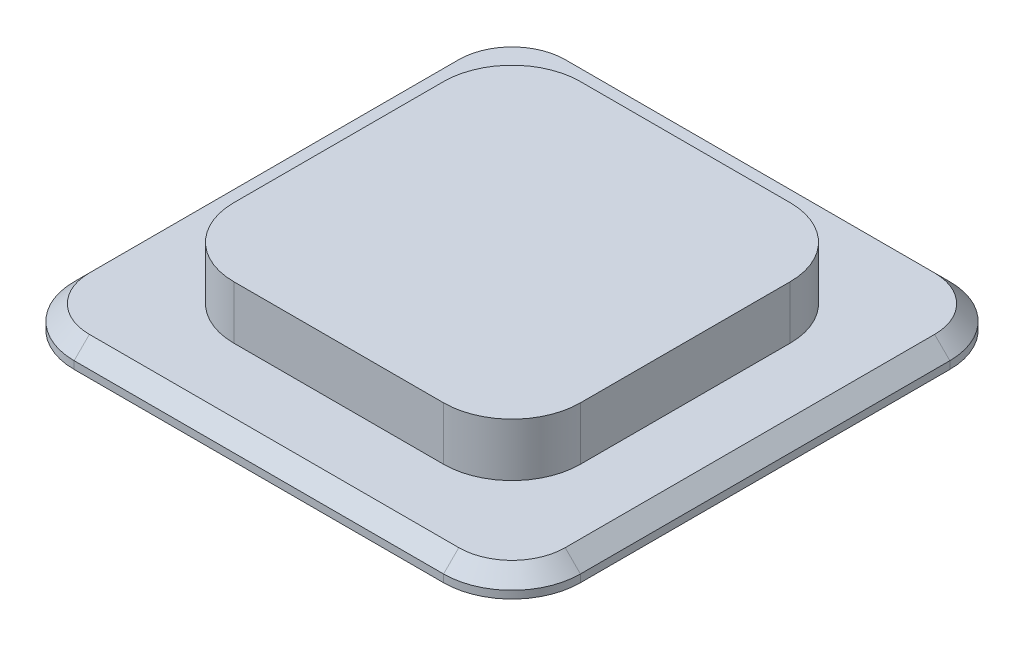
SolidWorks part; units mm, degrees
ref_plane "Front Plane" through (0, 0, 0) normal (0, 0, 1) x (1, 0, 0)
ref_plane "Top Plane" through (0, 0, 0) normal (0, 1, 0) x (1, 0, 0)
ref_plane "Right Plane" through (0, 0, 0) normal (1, 0, 0) x (0, 0, -1)
sketch "Sketch1" plane through (0, 0, 0) normal (0, 1, 0) x (1, 0, 0)
  line L1 (-16.65, -16.65) -> (16.65, -16.65)
  line L2 (-16.65, -16.65) -> (-16.65, 16.65)
  line L3 (-16.65, 16.65) -> (16.65, 16.65)
  line L4 (16.65, -16.65) -> (16.65, 16.65)
  line L5 (-16.65, -16.65) -> (16.65, 16.65) construction
  line L6 (-16.65, 16.65) -> (16.65, -16.65) construction
  line L7 (-11.4, -11.4) -> (11.4, -11.4)
  line L8 (-11.4, -11.4) -> (-11.4, 11.4)
  line L9 (-11.4, 11.4) -> (11.4, 11.4)
  line L10 (11.4, -11.4) -> (11.4, 11.4)
  line L11 (-11.4, -11.4) -> (11.4, 11.4) construction
  line L12 (-11.4, 11.4) -> (11.4, -11.4) construction
  point P0 (0, 0)
  point P6 (0, 0)
  dimension "D1" = 33.3
  dimension "D2" = 33.3
  dimension "D3" = 22.8
  dimension "D4" = 22.8
extrude "Boss-Extrude1" add sketch "Sketch1" along normal blind 1.5 contours L7 L10 L9 L8 | L1 L4 L3 L2 L10 L7 L8 L9 region at (-16.1791, 0, 0) region at (0, 0, 0)
extrude "Boss-Extrude2" add sketch "Sketch1<3>" along normal blind 5 contours L7 L10 L9 L8 region at (0, 0, 0)
sketch "Sketch1<3>" plane through (0, 0, 0) normal (0, 1, 0) x (1, 0, 0) same geometry as "Sketch1"
fillet "Fillet1" radius 4.5 8 edges at (16.65, 0.75, 16.65) (11.4, 3.25, 11.4) (11.4, 3.25, -11.4) (16.65, 0.75, -16.65) (-16.65, 0.75, -16.65) (-11.4, 3.25, -11.4) (-11.4, 3.25, 11.4) (-16.65, 0.75, 16.65)
chamfer "Chamfer1" distance 1 angle 45 8 edges at (15.332, 1.5, -15.332) (16.65, 1.5, 0) (15.332, 1.5, 15.332) (0, 1.5, 16.65) (-15.332, 1.5, 15.332) (-16.65, 1.5, 0) (-15.332, 1.5, -15.332) (0, 1.5, -16.65)
